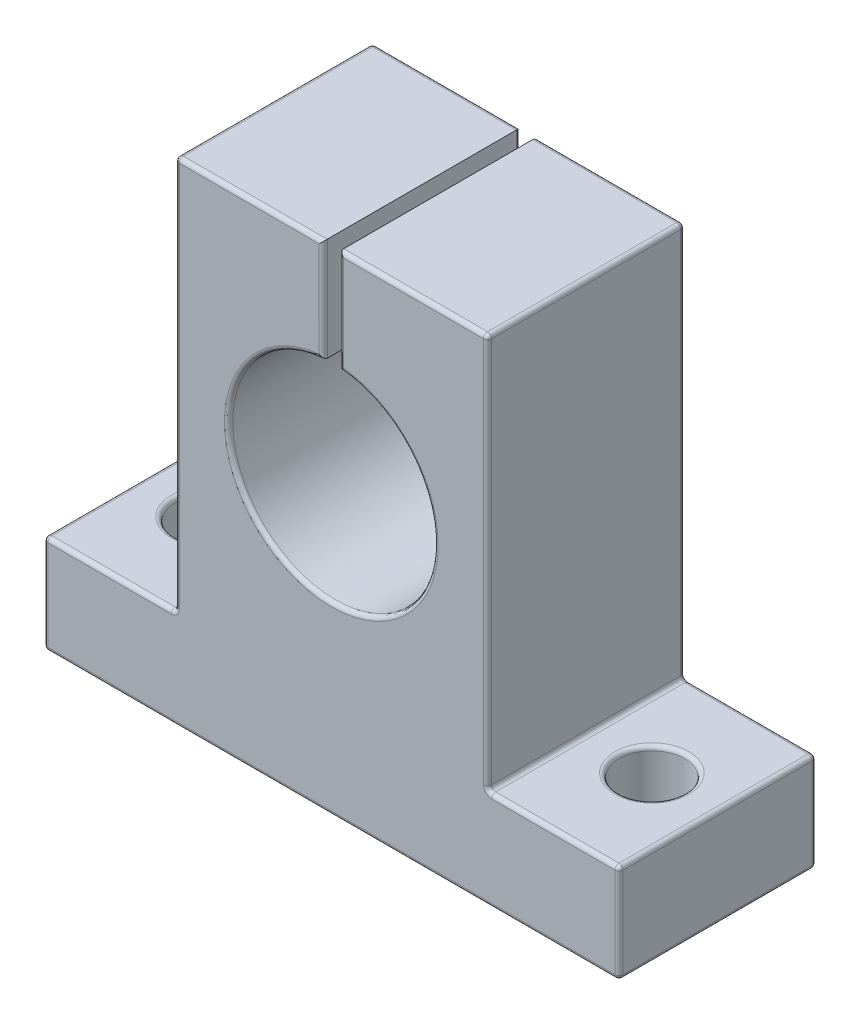
SolidWorks part; units mm, degrees
ref_plane "Płaszczyzna przednia" through (0, 0, 0) normal (0, 0, 1) x (1, 0, 0)
ref_plane "Płaszczyzna górna" through (0, 0, 0) normal (0, 1, 0) x (1, 0, 0)
ref_plane "Płaszczyzna prawa" through (0, 0, 0) normal (1, 0, 0) x (0, 0, -1)
sketch "Szkic1" plane through (0, 0, 0) normal (0, 0, 1) x (1, 0, 0)
  line L0 (19, 25) -> (19, -23)
  line L5 (-35, -23) -> (-35, -35)
  line L6 (-19, -23) -> (-35, -23)
  line L7 (19, -23) -> (35, -23)
  line L8 (0, 65.2796) -> (0, -54.227) construction
  line L9 (35, -23) -> (35, -35)
  line L10 (19, 25) -> (1, 25)
  line L11 (35, -35) -> (-35, -35)
  line L12 (-19, 25) -> (-19, -23)
  line L13 (-1, 25) -> (-1, 12.4599)
  line L14 (1, 25) -> (1, 12.4599)
  line L15 (-1, 25) -> (-19, 25)
  arc A0 (-1, 12.4599) -> (1, 12.4599) centre (0, 0) ccw
  point P0 (0, 0)
  point P2 (0, -35)
  point P14 (0, 0)
  dimension "D5" = 25
  dimension "D1" = 60
  dimension "D2" = 35
  dimension "D3" = 38
  dimension "D4" = 12
  dimension "D6" = 35
  dimension "D7" = 1
extrude "Dodanie-wyciągnięcie1" add sketch "Szkic1" along normal blind 12 and the other way blind 12
sketch "Szkic2" plane through (0, -23, 0) normal (0, 1, 0) x (1, 0, 0)
  line L0 (35, 12) -> (35, -12) construction
  line L1 (35, 12) -> (19, 12) construction
  circle A0 centre (27, 0) radius 4
  point P5 (35, 0)
  point P8 (27, 12)
  dimension "D1" = 8
extrude "Wytnij-wyciągnięcie1" cut sketch "Szkic2" against normal up to next
mirror "Lustro1" about plane through (0, 0, 0) normal (1, 0, 0) of "Wytnij-wyciągnięcie1"
fillet "Zaokrąglenie1" radius 0.5 34 edges at (-35, -35, 0) (-19, 25, 0) (-19, -23, 0) (-35, -23, 0) (-27, -23, 4) (10, 25, -12) (1, 18.73, -12) (0, -12.5, -12) (-1, 18.73, -12) (-10, 25, -12) (-19, 1, -12) (-27, -23, -12) (-35, -29, -12) (0, -35, -12) (35, -29, -12) (35, -35, 0) (27, -23, -12) (35, -23, 0) (27, -23, 4) (19, 1, -12) (19, -23, 0) (19, 25, 0) (-35, -29, 12) (-27, -23, 12) (-19, 1, 12) (-10, 25, 12) (-1, 18.73, 12) (0, -12.5, 12) (1, 18.73, 12) (10, 25, 12) (19, 1, 12) (27, -23, 12) (35, -29, 12) (0, -35, 12)
